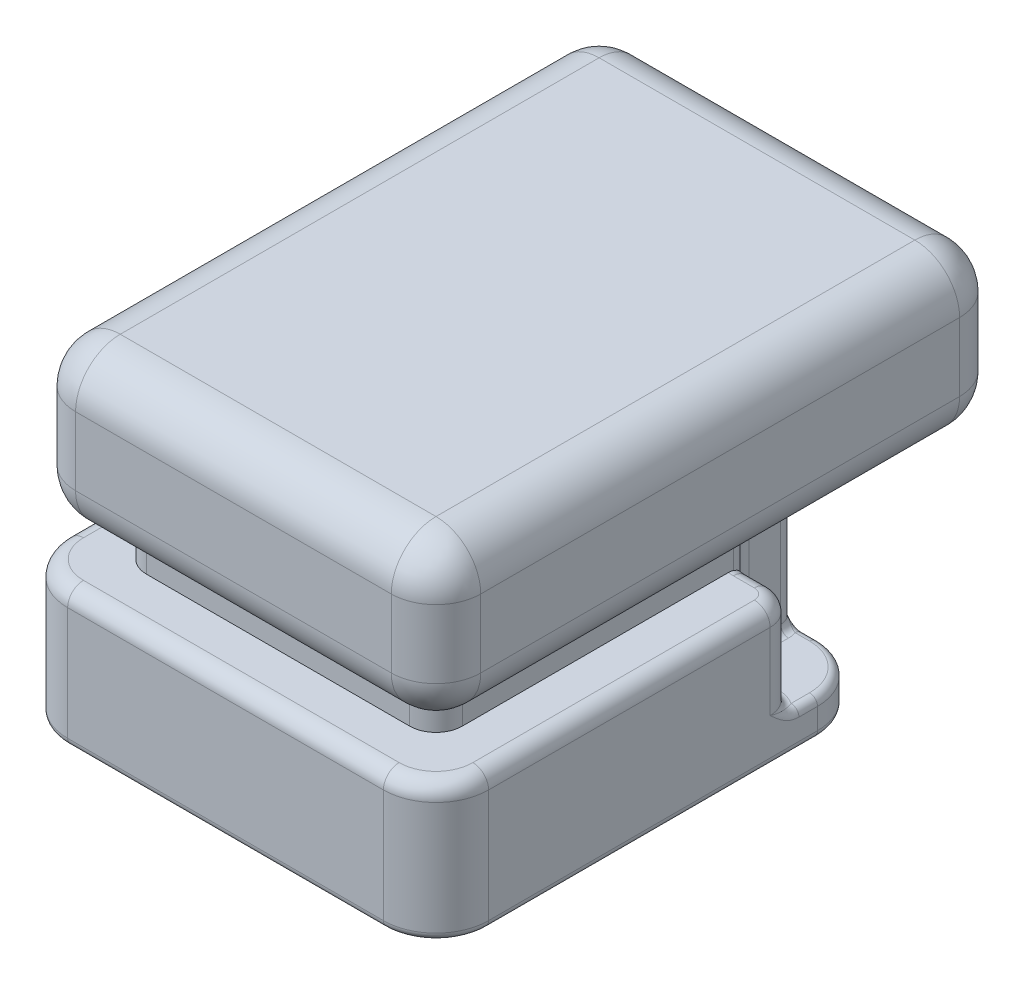
SolidWorks part; units mm, degrees
ref_plane "Front Plane" through (0, 0, 0) normal (0, 0, 1) x (1, 0, 0)
ref_plane "Top Plane" through (0, 0, 0) normal (0, 1, 0) x (1, 0, 0)
ref_plane "Right Plane" through (0, 0, 0) normal (1, 0, 0) x (0, 0, -1)
sketch "Sketch1" plane through (0, 0, 0) normal (0, 1, 0) x (1, 0, 0)
  line L1 (-40, -41.25) -> (40, -41.25)
  line L2 (-40, -41.25) -> (-40, 41.25)
  line L3 (-40, 41.25) -> (40, 41.25)
  line L4 (40, -41.25) -> (40, 41.25)
  line L5 (-40, -41.25) -> (40, 41.25) construction
  line L6 (-40, 41.25) -> (40, -41.25) construction
  point P0 (0, 0)
  dimension "D1" = 82.5
  dimension "D2" = 80
extrude "Boss-Extrude1" add sketch "Sketch1" along normal blind 32
sketch "Sketch2" plane through (0, 32, 0) normal (0, 1, 0) x (1, 0, 0)
  line L0 (40, 41.25) -> (-40, 41.25) construction
  line L1 (-20, -23.25) -> (20, -23.25)
  line L2 (-20, -23.25) -> (-20, 41.25)
  line L3 (-20, 41.25) -> (20, 41.25)
  line L4 (20, -23.25) -> (20, 41.25)
  line L5 (-40, -41.25) -> (40, -41.25) construction
  point P8 (0, -23.25)
  dimension "D1" = 40
  dimension "D2" = 18
extrude "Cut-Extrude1" cut sketch "Sketch2" against normal blind 13
sketch "Sketch3" plane through (0, 32, 0) normal (0, 1, 0) x (1, 0, 0)
  line L0 (-20, 41.25) -> (-40, 41.25) construction
  line L1 (-26, 41.25) -> (-40, 41.25)
  line L2 (-26, 41.25) -> (-26, 27.25)
  line L3 (-26, 27.25) -> (-40, 27.25)
  line L4 (-40, 41.25) -> (-40, 27.25)
  line L5 (-40, 41.25) -> (-40, -41.25) construction
  line L6 (40, 41.25) -> (20, 41.25) construction
  line L7 (26, 41.25) -> (40, 41.25)
  line L8 (26, 41.25) -> (26, 27.25)
  line L9 (26, 27.25) -> (40, 27.25)
  line L10 (40, 41.25) -> (40, 27.25)
  line L11 (40, -41.25) -> (40, 41.25) construction
  point P16 (27.2533, 28.5033)
  dimension "D1" = 14
extrude "Cut-Extrude2" cut sketch "Sketch3" against normal blind 25
sketch "Sketch4" plane through (0, 32, 0) normal (0, 1, 0) x (1, 0, 0)
  line L0 (-40, 27.25) -> (-30, 27.25)
  line L1 (-40, 27.25) -> (-26, 27.25) construction
  line L2 (-30, 27.25) -> (-30, -31.25)
  line L3 (-30, -31.25) -> (30, -31.25)
  line L4 (30, -31.25) -> (30, 27.25)
  line L5 (26, 27.25) -> (40, 27.25) construction
  line L6 (30, 27.25) -> (40, 27.25)
  line L7 (40, 27.25) -> (40, -41.25)
  line L8 (40, -41.25) -> (-40, -41.25)
  line L9 (-40, -41.25) -> (-40, 27.25)
  line L10 (0, -31.25) -> (0, -41.25) construction
  dimension "D1" = 10
extrude "Cut-Extrude3" cut sketch "Sketch4" against normal blind 6
sketch "Sketch5" plane through (0, 0, 0) normal (0, -1, 0) x (1, 0, 0)
  line L0 (-23, -21.25) -> (23, -21.25) construction
  line L2 (40, -41.25) -> (-40, -41.25) construction
  circle A0 centre (-23, -21.25) radius 1
  circle A1 centre (23, -21.25) radius 1
  point P6 (0, -21.25)
  dimension "D3" = 2
  dimension "D1" = 46
  dimension "D2" = 20
extrude "Cut-Extrude4" cut sketch "Sketch5" against normal blind 10
fillet "Fillet1" radius 10 4 edges at (40, 13, 41.25) (40, 3.5, -41.25) (-40, 3.5, -41.25) (-40, 13, 41.25)
fillet "Fillet2" radius 5 6 edges at (-26, 19.5, -27.25) (26, 19.5, -27.25) (-30, 29, 31.25) (30, 29, 31.25) (-40, 16.5, -27.25) (40, 16.5, -27.25)
fillet "Fillet3" radius 3 20 edges at (-30.4975, 26, -27.2753) (-33, 26, -27.25) (-38.5355, 26, -25.7855) (-40, 26, 4.5) (-37.0711, 26, 38.3211) (0, 26, 41.25) (37.0711, 26, 38.3211) (40, 26, 4.5) (30.4975, 26, -27.2753) (33, 26, -27.25) (26, 19.5, -41.25) (-26, 19.5, -41.25) (-30, 29, -27.351) (30, 29, -27.351) (38.5355, 26, -25.7855) (20, 25.5, 23.25) (-20, 25.5, 23.25) (-20, 25.5, -41.25) (20, 25.5, -41.25) (0, 19, -41.25)
fillet "Fillet4" radius 1.5 44 edges at (40, 7, -26.75) (26.5, 7, -41.25) (-26.5, 7, -41.25) (-40, 7, -26.75) (-40, 0, 0) (-37.0711, 0, 38.3211) (0, 0, 41.25) (37.0711, 0, 38.3211) (40, 0, 0) (37.0711, 0, -38.3211) (0, 0, -41.25) (-38.5355, 7, -25.7855) (-33, 7, -27.25) (-25.1213, 7, -40.3713) (-26, 7, -35.25) (25.1213, 7, -40.3713) (26, 7, -35.25) (38.5355, 7, -25.7855) (33, 7, -27.25) (26, 32, -35.25) (26.6699, 32, -29.75) (29.5981, 32, -26.8218) (30, 32, 0.4641) (28.5355, 32, 29.7855) (0, 32, 31.25) (-28.5355, 32, 29.7855) (-30, 32, 0.4641) (-29.5981, 32, -26.8218) (-26.6699, 32, -29.75) (-26, 32, -35.25) (-25.1213, 32, -40.3713) (-20.8787, 32, -40.3713) (-20, 32, -9) (-19.1213, 32, 22.3713) (0, 32, 23.25) (19.1213, 32, 22.3713) (20, 32, -9) (20.8787, 32, -40.3713) (25.1213, 32, -40.3713) (37.0711, 7, -38.3211) (-37.0711, 7, -38.3211) (-37.0711, 0, -38.3211) (-27.4645, 7, -28.7145) (27.4645, 7, -28.7145)
sketch "Sketch6" plane through (0, 19, 0) normal (0, 1, 0) x (1, 0, 0)
  line L4 (20, -20.25) -> (20, 38.25)
  line L5 (20, 38.25) -> (-20, 38.25)
  line L6 (-20, 38.25) -> (-20, -20.25)
  line L7 (-17, -23.25) -> (17, -23.25)
  line L8 (20, -20.25) -> (20, 38.25)
  line L9 (20, 38.25) -> (-20, 38.25)
  line L10 (-20, 38.25) -> (-20, -20.25)
  line L11 (-17, -23.25) -> (17, -23.25)
  arc A2 (-20, -20.25) -> (-17, -23.25) centre (-17, -20.25) ccw
  arc A3 (17, -23.25) -> (20, -20.25) centre (17, -20.25) ccw
  arc A4 (-20, -20.25) -> (-17, -23.25) centre (-17, -20.25) ccw
  arc A5 (17, -23.25) -> (20, -20.25) centre (17, -20.25) ccw
  dimension "D1" = 0
extrude "Boss-Extrude2" add sketch "Sketch6" along normal blind 14 separate body
sketch "Sketch7" plane through (0, 33, 0) normal (0, 1, 0) x (1, 0, 0)
  line L0 (-38.5, 68.25) -> (38.5, 68.25)
  line L1 (20, 38.25) -> (-20, 38.25) construction
  line L4 (-38.5, 31.25) -> (-38.5, -31.25)
  line L5 (30, 39.75) -> (-30, 39.75)
  line L6 (38.5, -31.25) -> (38.5, 31.25)
  line L7 (-30, -39.75) -> (30, -39.75)
  line L8 (-38.5, 68.25) -> (-38.5, -31.25)
  line L10 (38.5, -31.25) -> (38.5, 68.25)
  line L11 (-30, -39.75) -> (30, -39.75)
  arc A4 (-38.5, -31.25) -> (-30, -39.75) centre (-30, -31.25) ccw
  arc A5 (-30, 39.75) -> (-38.5, 31.25) centre (-30, 31.25) ccw
  arc A6 (38.5, 31.25) -> (30, 39.75) centre (30, 31.25) ccw
  arc A7 (30, -39.75) -> (38.5, -31.25) centre (30, -31.25) ccw
  arc A8 (-38.5, -31.25) -> (-30, -39.75) centre (-30, -31.25) ccw
  arc A11 (30, -39.75) -> (38.5, -31.25) centre (30, -31.25) ccw
  dimension "D2" = 30
  dimension "D1" = 0
extrude "Boss-Extrude3" add sketch "Sketch7" along normal blind 30
fillet "Fillet5" radius 8.5 14 edges at (38.5, 33, -18.5) (36.0104, 33, 37.2604) (0, 33, 39.75) (-36.0104, 33, 37.2604) (-38.5, 63, -18.5) (0, 63, -68.25) (38.5, 63, -18.5) (36.0104, 63, 37.2604) (0, 63, 39.75) (-36.0104, 63, 37.2604) (0, 33, -68.25) (-38.5, 33, -18.5) (38.5, 48, -68.25) (-38.5, 48, -68.25)
